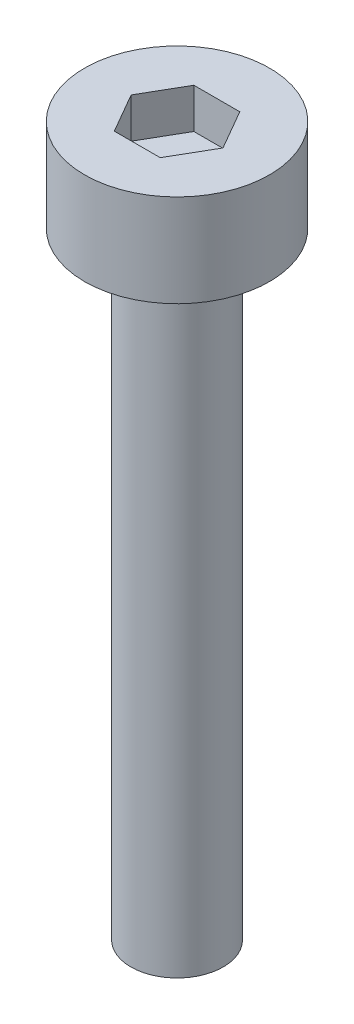
SolidWorks part; units mm, degrees
ref_plane "Front Plane" through (0, 0, 0) normal (0, 0, 1) x (1, 0, 0)
ref_plane "Top Plane" through (0, 0, 0) normal (0, 1, 0) x (1, 0, 0)
ref_plane "Right Plane" through (0, 0, 0) normal (1, 0, 0) x (0, 0, -1)
sketch "Sketch1" plane through (0, 0, 0) normal (0, 1, 0) x (1, 0, 0)
  circle A0 centre (0, 0) radius 1.5
  dimension "D1" = 3
extrude "ScrewShaft" add sketch "Sketch1" along normal blind 20
sketch "Sketch2" plane through (0, 20, 0) normal (0, 1, 0) x (1, 0, 0)
  circle A0 centre (0, 0) radius 3
  dimension "D1" = 6
extrude "Boss-Extrude2" add sketch "Sketch2" along normal blind 3
sketch "Sketch3" plane through (0, 23, 0) normal (0, 1, 0) x (1, 0, 0)
  line L0 (0, 0) -> (0, 1.29) construction
  line L1 (1.4896, 0) -> (0.7448, 1.29)
  line L2 (0.7448, 1.29) -> (-0.7448, 1.29)
  line L3 (-0.7448, 1.29) -> (-1.4896, 0)
  line L4 (-1.4896, 0) -> (-0.7448, -1.29)
  line L5 (-0.7448, -1.29) -> (0.7448, -1.29)
  line L6 (0.7448, -1.29) -> (1.4896, 0)
  circle A0 centre (0, 0) radius 1.29 construction
  dimension "D1" = 2.58
extrude "Cut-Extrude1" cut sketch "Sketch3" against normal blind 1.3
equation "\"X-ROD-SPACING\"=45"
equation "\"Y-ROD-SPACING\"=75"
equation "\"Z-ROD-SPACING\"=17.5"
equation "\"Y-BED-OFFSET\"=2"
equation "\"Y-BED-ROD-INSET\"=3.5"
equation "\"T-SLOT-NUT-FILLET-RADIUS\"=0.5"
equation "\"T-SLOT-SCREW-SHAFT-RADIUS\"=1.55"
equation "\"T-SLOT-SCREW-SHAFT-CUTOUT-LENGTH\"=11.0"
equation "\"T-SLOT-NUT-DEPTH\"=3.5"
equation "\"T-SLOT-NUT-WIDTH\"=2.85"
equation "\"T-SLOT-NUT-END-DISTANCE\"=8"
equation "\"ACRYLIC-THICKNESS\"=10"
equation "\"ACRYLIC-THICKNESS2\"=4.5"
equation "\"ACRYLIC-TAB-CUTOUT-SIZE\"=\"ACRYLIC-THICKNESS\"+\"ACRYLIC-TAB-TOLERANCE\"*2"
equation "\"ACRYLIC-TAB-WIDTH\"=\"ACRYLIC-THICKNESS\""
equation "\"ACRYLIC-M3-HOLE\"=2.9"
equation "\"SMOOTHROD-CAP-SCREW-DISTANCE\"=20"
equation "\"FRAME-WIDTH-INNER\"=370"
equation "\"NEMA17-HOLE-SPACING\"=31"
equation "\"NEMA17-CENTRAL-CUTOUT\"=22.5"
equation "\"Z-BRACKET-REACH\"=55"
equation "\"TOP-BRACKET-SPACING\"=40"
equation "\"SMOOTHROD-X-LENGTH\"=350"
equation "\"SMOOTHROD-Y-LENGTH\"=350"
equation "\"SMOOTHROD-Z-LENGTH\"=350"
equation "\"SMOOTHROD-TIGHTENING-HEADROOM\"=.25"
equation "\"LEADSCREW-Z-LENGTH\"=300"
equation "\"SCREW-LENGTH-FRAME\"=\"ACRYLIC-THICKNESS\" + 10"
equation "\"SCREW-HEAD-RADIUS\"=6"
equation "\"PRINTED-X-SMOOTHROD-DIAMETER\"=9.0"
equation "\"PRINTED-X-SMOOTHROD-CUTOUT\"=10"
equation "\"PRINTED-X-BASE-HEIGHT\"=10"
equation "\"PRINTED-LM8UU-CUTOUT-SIZE\"=15.5"
equation "\"PRINTED-LM8UU-CUTOUT-LENGTH\"=24.5"
equation "\"PRINTED-X-IDLER-HEIGHT\"=16"
equation "\"PSU-MOUNTING-WIDTH\"=95"
equation "\"PSU-MOUNTING-HEIGHT\"=177"
equation "\"D1@ScrewShaft\"=\"SCREW-LENGTH-FRAME\""
equation "\"D1@Sketch2\"=\"SCREW-HEAD-RADIUS\""
